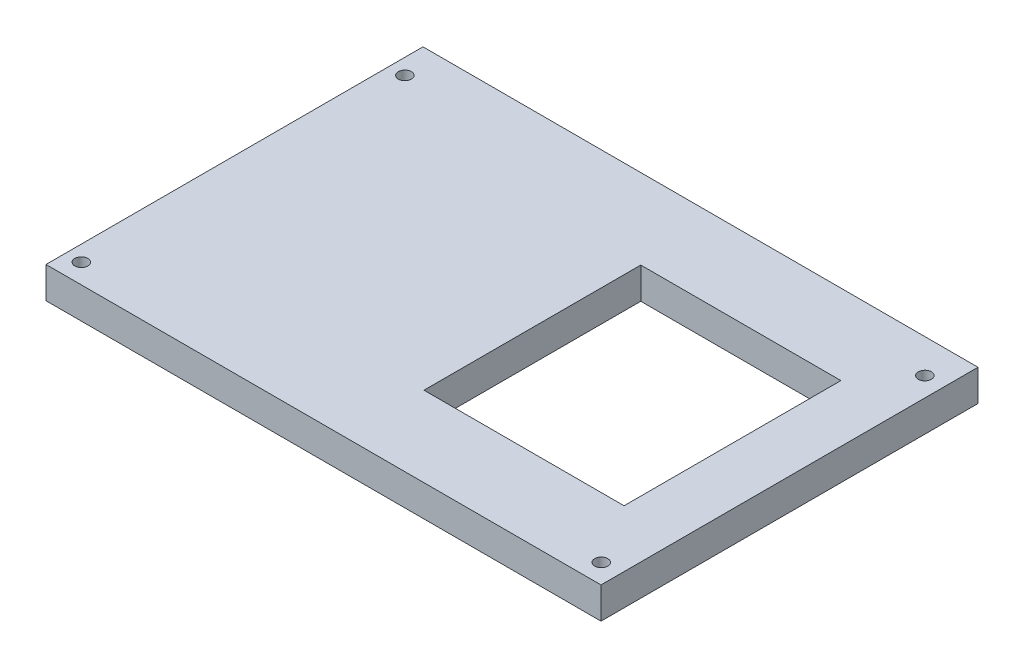
SolidWorks part; units mm, degrees
ref_plane "Front Plane" through (0, 0, 0) normal (0, 0, 1) x (1, 0, 0)
ref_plane "Top Plane" through (0, 0, 0) normal (0, 1, 0) x (1, 0, 0)
ref_plane "Right Plane" through (0, 0, 0) normal (1, 0, 0) x (0, 0, -1)
sketch "Sketch2" plane through (0, 0, 0) normal (0, 0, 1) x (1, 0, 0)
  line L1 (-53, 3) -> (53, 3)
  line L2 (-53, 3) -> (-53, -3)
  line L3 (-53, -3) -> (53, -3)
  line L4 (53, 3) -> (53, -3)
  line L5 (-53, 3) -> (53, -3) construction
  line L6 (-53, -3) -> (53, 3) construction
  point P0 (0, 0)
  dimension "D1" = 106
  dimension "D2" = 6
extrude "Boss-Extrude1" add sketch "Sketch2" along normal blind 72
sketch "Sketch4" plane through (0, 3, 0) normal (0, 1, 0) x (1, 0, 0)
  line L0 (-53, -72) -> (53, -72) construction
  line L1 (53, -72) -> (53, 0) construction
  line L2 (-62.6793, -72) -> (-62.6793, -4) construction
  line L3 (-50.0049, -4) -> (-53, -4) construction
  line L4 (-53, -72) -> (-53, 0) construction
  line L5 (-53, -4) -> (53, -4) construction
  line L6 (-56.8726, -4) -> (-56.8726, -6.4507) construction
  line L7 (-55.3882, -72) -> (-55.3882, -68.2507) construction
  line L8 (53, -77.5021) -> (49.2951, -77.5021) construction
  line L9 (53, 3.1613) -> (49.2951, 3.1613) construction
  line L10 (-53.7098, 3.1613) -> (-50.0049, 3.1613) construction
  line L11 (-53, -36) -> (53, -36) construction
  line L12 (0, 0) -> (0, -72) construction
  line L13 (53, 0) -> (-53, 0) construction
  circle A0 centre (-50.0049, -68.2507) radius 1.25
  circle A1 centre (49.2951, -68.2507) radius 1.25
  circle A2 centre (49.2951, -6.4507) radius 1.25
  circle A3 centre (-50.0049, -6.4507) radius 1.25
  dimension "D6" = 2.5
  dimension "D1" = 106
  dimension "D2" = 72
  dimension "D3" = 68
  dimension "D4" = 99.3
  dimension "D5" = 61.8
extrude "Cut-Extrude1" cut sketch "Sketch4" against normal through all contours A3 | A0 | A1 | A2 region at (-50.0049, 3, 68.2507) region at (49.2951, 3, 68.2507) region at (49.2951, 3, 6.4507) region at (-50.0049, 3, 6.4507)
sketch "Sketch5" plane through (0, 0, 0) normal (0, 0, -1) x (-1, 0, 0)
  line L0 (-53, 0) -> (53, 0) construction
  line L1 (-53, -3) -> (-53, 3) construction
  line L2 (53, 3) -> (53, -3) construction
  circle A0 centre (0, 0) radius 1.75
  circle A1 centre (26.5, 0) radius 1.75
  circle A2 centre (-26.5, 0) radius 1.75
  dimension "D3" = 3.5
  dimension "D1" = 26.5
  dimension "D2" = 26.5
extrude "Cut-Extrude2" cut sketch "Sketch5" against normal blind 10
sketch "Sketch6" plane through (0, 3, 0) normal (0, 1, 0) x (1, 0, 0)
  line L0 (0, 0) -> (0, -72) construction
  line L1 (53, -72) -> (-53, -72) construction
  line L2 (-53, -36) -> (53, -36) construction
  line L3 (-53, -72) -> (-53, 0) construction
  line L4 (53, -72) -> (53, 0) construction
  line L6 (3.8895, -15.2958) -> (42.1105, -15.2958)
  line L7 (3.8895, -15.2958) -> (3.8895, -56.7042)
  line L8 (3.8895, -56.7042) -> (42.1105, -56.7042)
  line L9 (42.1105, -15.2958) -> (42.1105, -56.7042)
  line L10 (3.8895, -15.2958) -> (42.1105, -56.7042) construction
  line L11 (3.8895, -56.7042) -> (42.1105, -15.2958) construction
  point P11 (23, -36)
  point P18 (51.4007, -36.8248)
  dimension "D1" = 23
  dimension "D2" = 30
extrude "Cut-Extrude3" cut sketch "Sketch6" against normal blind 10
